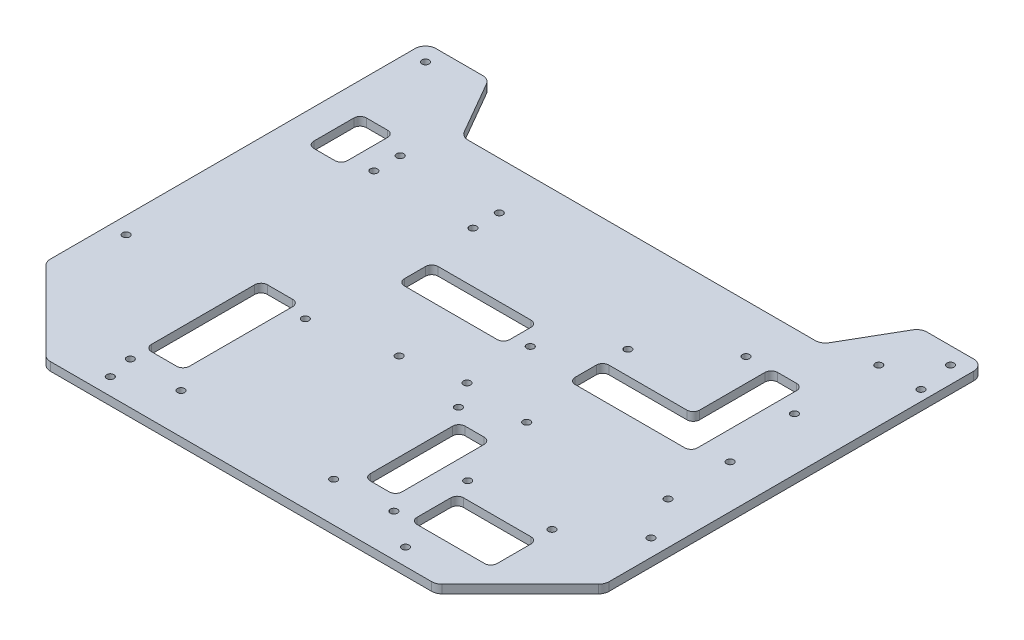
SolidWorks part; units mm, degrees
material "Acier non allié"
ref_plane "Front" through (0, 0, 0) normal (0, 0, 1) x (1, 0, 0)
ref_plane "Top" through (0, 0, 0) normal (0, 1, 0) x (1, 0, 0)
ref_plane "Right" through (0, 0, 0) normal (1, 0, 0) x (0, 0, -1)
sketch "Main scetch" plane through (0, 0, 0) normal (0, 1, 0) x (1, 0, 0)
  line L1 (0, 0) -> (132.5, 0) construction
  line L2 (0, 0) -> (0, 220) construction
  line L3 (0, 220) -> (132.5, 220) construction
  line L4 (132.5, 0) -> (132.5, 220) construction
  line L13 (-92.5, 0) -> (92.5, 0)
  line L14 (92.5, 0) -> (132.5, 40)
  line L15 (132.5, 40) -> (132.5, 220)
  line L16 (132.5, 220) -> (102.5, 220)
  line L17 (102.5, 220) -> (85.1795, 190)
  line L18 (85.1795, 190) -> (-85.1795, 190)
  line L19 (-102.5, 220) -> (-85.1795, 190)
  line L20 (-132.5, 220) -> (-102.5, 220)
  line L21 (-132.5, 40) -> (-132.5, 220)
  line L22 (-92.5, 0) -> (-132.5, 40)
  point P11 (0, 190)
  dimension "132.5" = 132.5
  dimension "D2" = 220
  dimension "D1" = 40
  dimension "D3" = 40
  dimension "D4" = 30
  dimension "D5" = 60
  dimension "D6" = 30
extrude "Main extrusion" add sketch "Main scetch" along normal blind 4
fillet "Congé1" radius 5 10 edges at (-132.5, 2, -40) (-92.5, 2, 0) (92.5, 2, 0) (132.5, 2, -40) (132.5, 2, -220) (102.5, 2, -220) (85.1795, 2, -190) (-85.1795, 2, -190) (-102.5, 2, -220) (-132.5, 2, -220)
sketch "Esquisse1" plane through (0, 4, 0) normal (0, 1, 0) x (1, 0, 0)
  line L0 (0, 0) -> (0, 218.5516) construction
  line L1 (132.5, 42.0711) -> (132.5, 215) construction
  line L2 (127.5, 220) -> (105.3868, 220) construction
  line L3 (-90.4289, 0) -> (90.4289, 0) construction
  circle A0 centre (70, 8) radius 1
  circle A1 centre (124.5, 70) radius 1
  circle A2 centre (124.5, 212) radius 1
  circle A3 centre (-124.5, 212) radius 1
  circle A4 centre (-124.5, 70) radius 1
  circle A5 centre (-70, 8) radius 1
  dimension "D1" = 2
  dimension "D2" = 2
  dimension "D3" = 2
  dimension "D4" = 8
  dimension "D5" = 8
  dimension "D6" = 8
  dimension "D7" = 8
  dimension "D8" = 70
  dimension "D9" = 70
extrude "Enlèv. mat.-Extru.1" cut sketch "Esquisse1" against normal through all
hole_wizard "Dégagement M31" positions "Esquisse2" profile "Esquisse3" hole size "M3" standard "ISO" end condition through all
sketch "Esquisse2" plane through (0, 4, 0) normal (0, 1, 0) x (1, 0, 0)
  point P0 (-124.5, 212)
  point P3 (-124.5, 70)
  point P6 (-70, 8)
  point P9 (70, 8)
  point P12 (124.5, 70)
  point P15 (124.5, 212)
sketch "Esquisse3" plane through (-124.5, 4, -212) normal (1, 0, 0) x (0, 0, 1)
  line L0 (0, 0) -> (0, 4)
  line L1 (0, 4) -> (1.7, 4)
  line L2 (1.7, 4) -> (1.7, 0)
  line L5 (1.7, 0) -> (0, 0)
  line L11 (0, -6.35) -> (0, 107.95) construction
  dimension "Diamètre du perçage jusqu'au prochain" = 3.4
  dimension "Profondeur du perçage jusqu'au prochain" = 4
sketch "Esquisse4" plane through (0, 4, 0) normal (0, 1, 0) x (1, 0, 0)
  line L0 (-132.5, 215) -> (-132.5, 42.0711) construction
  line L2 (82.2927, 190) -> (-82.2927, 190) construction
  line L3 (132.5, 42.0711) -> (132.5, 215) construction
  line L4 (-90.4289, 0) -> (90.4289, 0) construction
  line L5 (127.5, 220) -> (105.3868, 220) construction
  circle A1 centre (-68.5, 185) radius 1 construction
  circle A5 centre (72.5, 167) radius 1
  circle A6 centre (41.5, 142) radius 1
  circle A7 centre (107.5, 155) radius 1
  circle A8 centre (127.5, 195) radius 1
  circle A9 centre (112, 120) radius 1
  circle A10 centre (112.5, 90) radius 1
  circle A11 centre (17.2, 120) radius 1
  circle A12 centre (17.2, 90) radius 1
  circle A13 centre (47.5, 88) radius 1
  circle A14 centre (57.5, 50) radius 1
  circle A15 centre (97.5, 50) radius 1
  circle A16 centre (52.5, 20) radius 1
  circle A17 centre (-10, 85) radius 1
  circle A18 centre (-72.5, 20) radius 1
  circle A19 centre (107.5, 195) radius 1
  circle A23 centre (-47.5, 78) radius 1
  circle A24 centre (25.14, 78) radius 1
  circle A25 centre (-47.5, 19.07) radius 1
  circle A26 centre (25.1096, 18.82) radius 1
  circle A27 centre (-92, 167.5) radius 1
  circle A28 centre (-45, 167.5) radius 1
  circle A29 centre (-92, 155) radius 1
  circle A30 centre (-45, 155) radius 1
  dimension "D4" = 2
  dimension "D13" = 2
  dimension "D16" = 2
  dimension "D19" = 2
  dimension "D24" = 2
  dimension "D25" = 2
  dimension "D28" = 2
  dimension "D30" = 2
  dimension "D32" = 2
  dimension "D36" = 2
  dimension "D37" = 2
  dimension "D40" = 2
  dimension "D48" = 2
  dimension "D49" = 2
  dimension "D50" = 2
  dimension "D52" = 2
  dimension "D11" = 2
  dimension "D12" = 2
  dimension "D65" = 2
  dimension "D66" = 2
  dimension "D58" = 2
  dimension "D61" = 2
  dimension "D70" = 2
  dimension "D71" = 2
  dimension "D14" = 205
  dimension "D15" = 23
  dimension "D20" = 25
  dimension "D21" = 65
  dimension "D22" = 5
  dimension "D23" = 25
  dimension "D26" = 20.5
  dimension "D27" = 100
  dimension "D29" = 30
  dimension "D31" = 115.3
  dimension "D33" = 115.3
  dimension "D34" = 132
  dimension "D35" = 85
  dimension "D38" = 50
  dimension "D39" = 75
  dimension "D41" = 35
  dimension "D42" = 80
  dimension "D43" = 20
  dimension "D44" = 20
  dimension "D45" = 205
  dimension "D46" = 85
  dimension "D47" = 142.5
  dimension "D51" = 25
  dimension "D53" = 25
  dimension "D54" = 5
  dimension "D55" = 64
  dimension "D7" = 59.18
  dimension "D8" = 72.64
  dimension "D9" = 58.93
  dimension "D10" = 72.61
  dimension "D67" = 85
  dimension "D68" = 78
  dimension "D56" = 23.5
  dimension "D57" = 23.5
  dimension "D59" = 17.5
  dimension "D60" = 17.5
  dimension "D62" = 12.5
  dimension "D63" = 12.5
  dimension "D64" = 23.5
  dimension "D69" = 23.5
  dimension "D17" = 25
  dimension "D18" = 31
extrude "Enlèv. mat.-Extru.2" cut sketch "Esquisse4" against normal through all
hole_wizard "Dégagement M32" positions "Esquisse5" profile "Esquisse6" hole size "M3" standard "ISO" end condition through all
sketch "Esquisse5" plane through (0, 4, 0) normal (0, 1, 0) x (1, 0, 0)
  point P9 (17.2, 120)
  point P18 (41.5, 142)
  point P21 (72.5, 167)
  point P24 (107.5, 155)
  point P27 (127.5, 195)
  point P30 (112, 120)
  point P33 (112.5, 90)
  point P36 (47.5, 88)
  point P39 (17.2, 90)
  point P42 (57.5, 50)
  point P45 (97.5, 50)
  point P48 (-10, 85)
  point P51 (-72.5, 20)
  point P54 (52.5, 20)
  point P57 (107.5, 195)
  point P86 (-47.5, 78)
  point P89 (25.14, 78)
  point P92 (-47.5, 19.07)
  point P95 (25.1096, 18.82)
  point P102 (-92, 167.5)
  point P105 (-92, 155)
  point P108 (-45, 155)
  point P111 (-45, 167.5)
sketch "Esquisse6" plane through (17.2, 4, -120) normal (1, 0, 0) x (0, 0, 1)
  line L0 (0, 0) -> (0, 4)
  line L1 (0, 4) -> (1.7, 4)
  line L2 (1.7, 4) -> (1.7, 0)
  line L5 (1.7, 0) -> (0, 0)
  line L11 (0, -6.35) -> (0, 107.95) construction
  dimension "Diamètre du perçage jusqu'au prochain" = 3.4
  dimension "Profondeur du perçage jusqu'au prochain" = 4
sketch "Esquisse7" plane through (0, 4, 0) normal (0, 1, 0) x (1, 0, 0)
  line L0 (-90.4289, 0) -> (90.4289, 0) construction
  line L1 (-40.5, 131) -> (9.5, 131)
  line L2 (-40.5, 131) -> (-40.5, 115)
  line L3 (-40.5, 115) -> (9.5, 115)
  line L4 (9.5, 131) -> (9.5, 115)
  line L5 (-132.5, 215) -> (-132.5, 42.0711) construction
  line L8 (40.5, 115) -> (98.5, 115)
  line L10 (132.5, 42.0711) -> (132.5, 215) construction
  line L11 (40.5, 115) -> (40.5, 131)
  line L12 (83.5, 168) -> (98.5, 168)
  line L13 (83.5, 168) -> (83.5, 131)
  line L15 (98.5, 168) -> (98.5, 115)
  line L16 (40.5, 131) -> (83.5, 131)
  line L17 (-105.3868, 220) -> (-127.5, 220) construction
  line L18 (60.5, 42) -> (98.5, 42)
  line L19 (60.5, 42) -> (60.5, 20)
  line L20 (60.5, 20) -> (98.5, 20)
  line L21 (98.5, 42) -> (98.5, 20)
  line L22 (-118.5, 175) -> (-102.5, 175)
  line L23 (-118.5, 175) -> (-118.5, 150)
  line L24 (-118.5, 150) -> (-102.5, 150)
  line L25 (-102.5, 175) -> (-102.5, 150)
  line L27 (-73.5, 28) -> (-55.5, 28)
  line L28 (-73.5, 28) -> (-73.5, 83)
  line L29 (-73.5, 83) -> (-55.5, 83)
  line L30 (-55.5, 28) -> (-55.5, 83)
  line L31 (31.5, 71.82) -> (46.5, 71.82)
  line L32 (31.5, 71.82) -> (31.5, 26.82)
  line L33 (31.5, 26.82) -> (46.5, 26.82)
  line L34 (46.5, 71.82) -> (46.5, 26.82)
  circle A0 centre (-72.5, 20) radius 1.7 construction
  circle A1 centre (-47.5, 78) radius 1.7 construction
  circle A2 centre (25.1096, 18.82) radius 1.7 construction
  circle A3 centre (52.5, 20) radius 1.7 construction
  dimension "D19" = 8
  dimension "D20" = 8
  dimension "D24" = 15
  dimension "D1" = 50
  dimension "D2" = 16
  dimension "D3" = 131
  dimension "D4" = 92
  dimension "D5" = 16
  dimension "D6" = 53
  dimension "D7" = 43
  dimension "D8" = 115
  dimension "D9" = 72
  dimension "D10" = 38
  dimension "D11" = 34
  dimension "D12" = 15
  dimension "D13" = 22
  dimension "D14" = 20
  dimension "D15" = 30
  dimension "D16" = 70
  dimension "D17" = 16
  dimension "D18" = 25
  dimension "D21" = 18
  dimension "D22" = 55
  dimension "D23" = 8
  dimension "6" = 6
  dimension "D25" = 45
extrude "Enlèv. mat.-Extru.3" cut sketch "Esquisse7" against normal up to surface (4 mm away) up to face at (17.2, 0, -118.3)
fillet "Congé2" radius 3 26 edges at (60.5, 2, -42) (60.5, 2, -20) (98.5, 2, -20) (98.5, 2, -42) (98.5, 2, -168) (98.5, 2, -115) (83.5, 2, -168) (40.5, 2, -131) (83.5, 2, -131) (40.5, 2, -115) (-40.5, 2, -115) (9.5, 2, -115) (9.5, 2, -131) (-40.5, 2, -131) (-118.5, 2, -150) (-102.5, 2, -150) (-102.5, 2, -175) (-118.5, 2, -175) (-55.5, 2, -28) (-73.5, 2, -28) (-55.5, 2, -83) (-73.5, 2, -83) (46.5, 2, -26.82) (31.5, 2, -26.82) (46.5, 2, -71.82) (31.5, 2, -71.82)
equation "\"WIDTH\"= 300mm'Total width of the robot"
equation "\"LENGTH\"= 220mm'Total length of the robot"
equation "\"D2@Main scetch\" = \"LENGTH\""
equation "\"CUT_DEPTH\"= 45mm'Depth of the cut on the edges of the plate"
equation "\"Plate_th\"= 3mm'Thickness of the plate"
equation "\"D1\"= \"Plate_th\""
equation "\"D47@Esquisse4\"=(80+205)/2"
